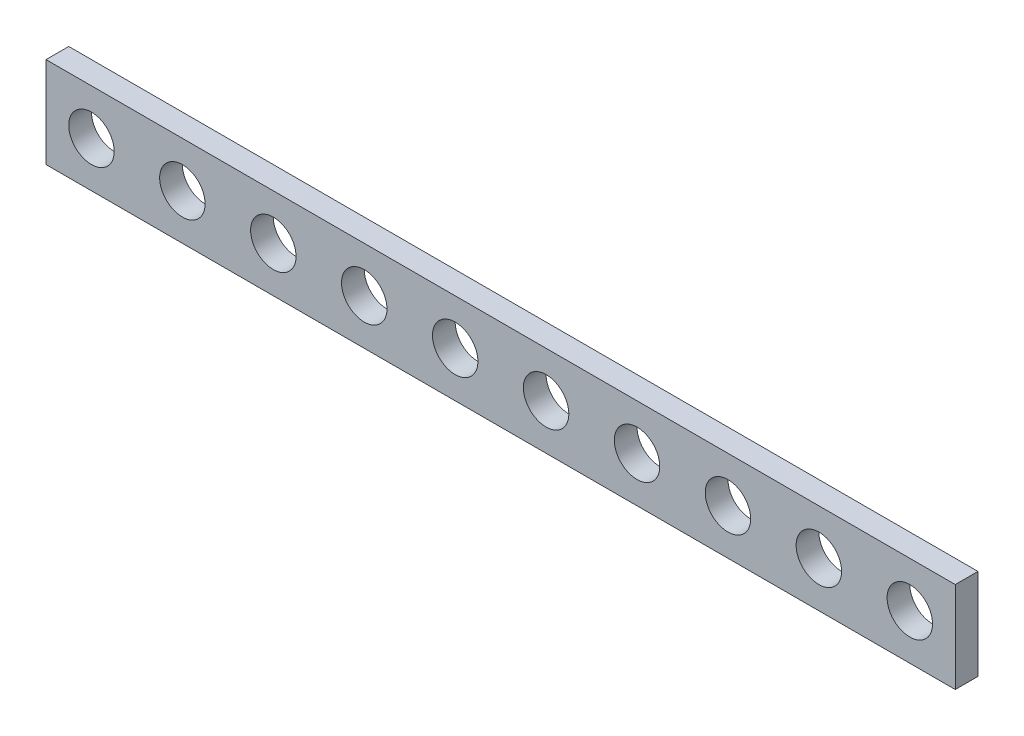
SolidWorks part; units mm, degrees
ref_plane "Płaszczyzna przednia" through (0, 0, 0) normal (0, 0, 1) x (1, 0, 0)
ref_plane "Płaszczyzna górna" through (0, 0, 0) normal (0, 1, 0) x (1, 0, 0)
ref_plane "Płaszczyzna prawa" through (0, 0, 0) normal (1, 0, 0) x (0, 0, -1)
sketch "Szkic2" plane through (0, 0, 0) normal (0, 0, 1) x (1, 0, 0)
  line L0 (0, 0) -> (200, 0)
  line L1 (0, 0) -> (0, 20)
  line L2 (0, 20) -> (200, 20)
  line L3 (200, 20) -> (200, 0)
  circle A0 centre (10, 10) radius 5
  dimension "ŚO" = 10
  dimension "SP" = 200
  dimension "WP" = 20
  dimension "OXO" = 10
  dimension "OYO" = 10
extrude "Dodanie-wyciągnięcie5" add sketch "Szkic2" along normal blind 5
pattern_linear "Szyk liniowy1" count 10 spacing 20 along (1, 0, 0) of face at (15, 10, 5)
equation "\"IPX@Szyk liniowy1\" = \"SP@Szkic2\" / 20"
equation "\"OdX@Szyk liniowy1\"= \"SP@Szkic2\" / \"IPX@Szyk liniowy1\""
